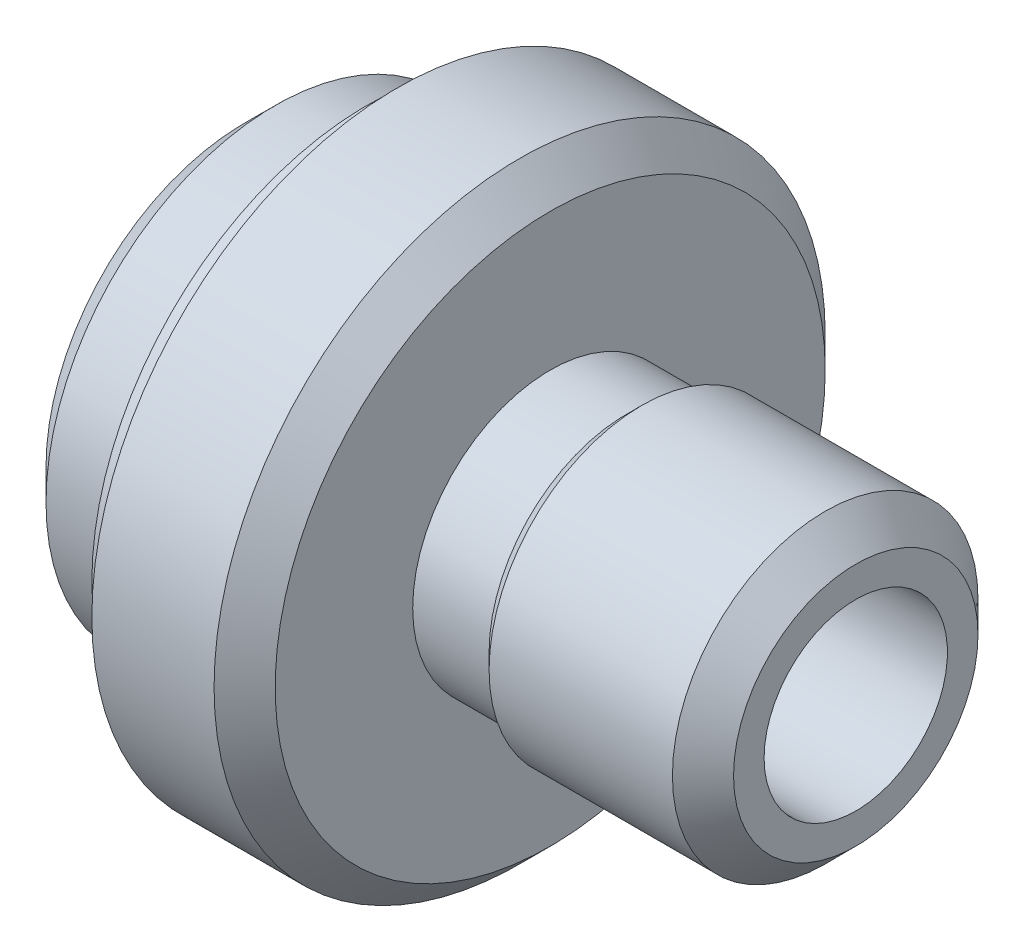
SolidWorks part; units mm, degrees
material "AA380.0-F matriz"
ref_plane "Plano frontal" through (0, 0, 0) normal (0, 0, 1) x (1, 0, 0)
ref_plane "Plano superior" through (0, 0, 0) normal (0, 1, 0) x (1, 0, 0)
ref_plane "Plano direito" through (0, 0, 0) normal (1, 0, 0) x (0, 0, -1)
sketch "Esboço1" plane through (0, 0, 0) normal (0, 0, 1) x (1, 0, 0)
  line L0 (0, 0) -> (0, -15)
  line L1 (0, -15) -> (8, -15)
  line L2 (8, -15) -> (8, -18)
  line L3 (8, -18) -> (10, -18)
  line L4 (10, -18) -> (10, -20)
  line L5 (10, -20) -> (20, -20)
  line L6 (20, -20) -> (20, -9)
  line L7 (20, -9) -> (24, -9)
  line L8 (24, -9) -> (24, -10)
  line L9 (24, -10) -> (40, -10)
  line L10 (40, -10) -> (40, 0)
  line L11 (0, 0) -> (40, 0)
  point P3 (0, 0)
  point P14 (0, 0)
  point P15 (0, 0)
  point P16 (0, 0)
  point P17 (0, 0)
  point P18 (0, 0)
  dimension "D1" = 15
  dimension "D2" = 18
  dimension "D3" = 9
  dimension "D4" = 10
  dimension "D5" = 20
  dimension "D6" = 8
  dimension "D7" = 10
  dimension "D8" = 4
  dimension "D9" = 10
  dimension "D10" = 20
revolve "Revolução1" add sketch "Esboço1" angle 360 about L11
chamfer "Chanfro1" distance 2 angle 45 3 edges at (20, 0, 20) (40, 0, 10) (0, 0, 15)
chamfer "Chanfro2" distance 2 angle 45 1 edges at (24, 0, 10)
sketch "Esboço2" plane through (0, 0, 0) normal (-1, 0, 0) x (0, 0, 1)
  circle A0 centre (0, 0) radius 6
  dimension "D1" = 12
extrude "Corte-extrusão1" cut sketch "Esboço2" against normal through all and the other way through all
